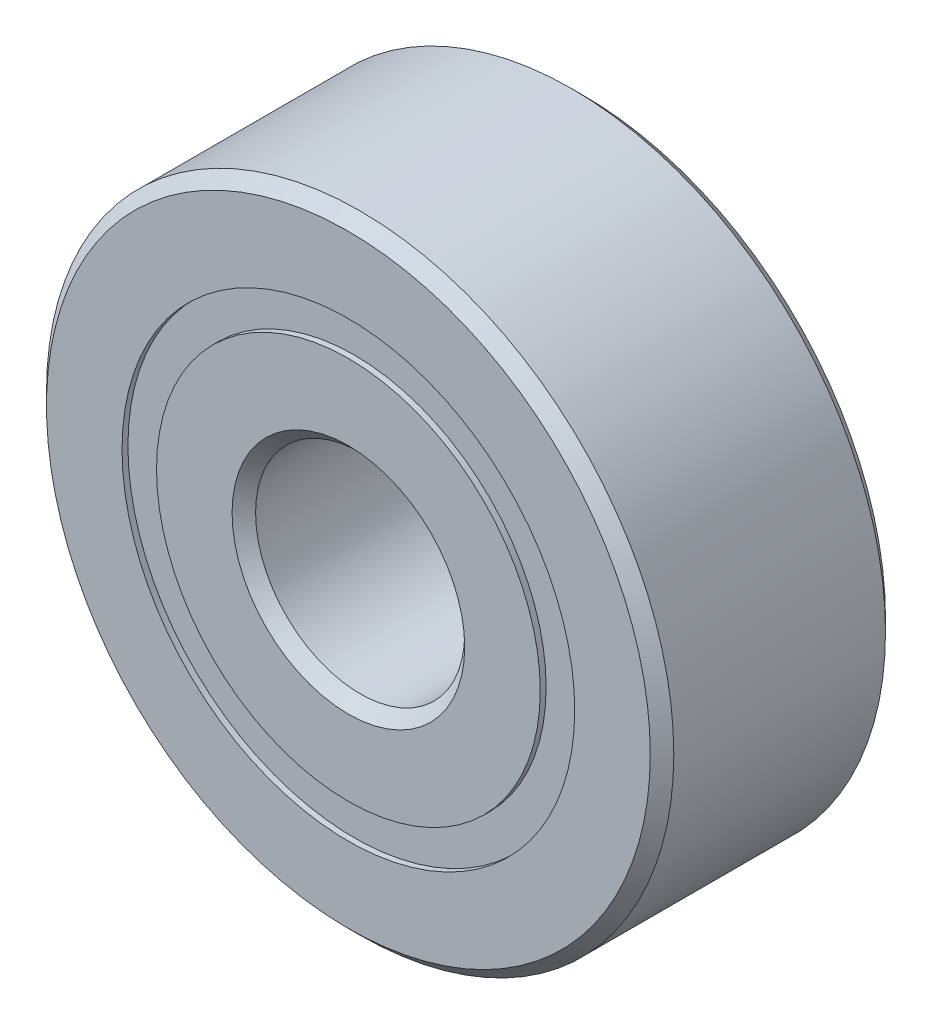
SolidWorks part; units mm, degrees
material "Cast Alloy Steel"
ref_plane "Front Plane" through (0, 0, 0) normal (0, 0, 1) x (1, 0, 0)
ref_plane "Top Plane" through (0, 0, 0) normal (0, 1, 0) x (1, 0, 0)
ref_plane "Right Plane" through (0, 0, 0) normal (1, 0, 0) x (0, 0, -1)
sketch "Sketch1" plane through (0, 0, 0) normal (1, 0, 0) x (0, 0, -1)
  line L0 (-3.5719, 0) -> (3.5719, 0) construction
  line L1 (0, 9.525) -> (0, -9.525) construction
  line L2 (3.2147, 9.525) -> (-3.2147, 9.525)
  line L3 (-3.2147, 9.525) -> (-3.5719, 9.1678)
  line L4 (-3.5719, 9.1678) -> (-3.5719, 6.8734)
  line L5 (-3.5719, 6.8734) -> (-1.5875, 6.8734)
  line L6 (3.5719, 6.8734) -> (1.5875, 6.8734)
  line L7 (3.5719, 9.1678) -> (3.5719, 6.8734)
  line L8 (3.2147, 9.525) -> (3.5719, 9.1678)
  line L9 (0, 9.525) -> (0, 6.35) construction
  line L10 (0, 6.35) -> (0, 3.175) construction
  arc A0 (-1.5875, 6.8734) -> (1.5875, 6.8734) centre (0, 6.35) cw
  point P14 (0, 3.175)
  dimension "Width" = 7.1437
  dimension "OD" = 19.05
  dimension "D1" = 45
  dimension "D2" = 0.3572
  dimension "Shaft Dia" = 6.35
  dimension "D3" = 3.175
  dimension "D4" = 0.5234
revolve "Revolve1" add sketch "Sketch1" angle 360 about L0
sketch "Sketch3" plane through (0, 0, 0) normal (1, 0, 0) x (0, 0, -1)
  line L0 (-3.5719, 5.8266) -> (-1.5875, 5.8266)
  line L1 (0, 9.525) -> (0, -9.525) construction
  line L2 (-3.5719, 9.1678) -> (-3.5719, 6.8734) construction
  line L3 (-3.5719, 5.8266) -> (-3.5719, 3.5322)
  line L4 (-3.2147, 9.525) -> (-3.5719, 9.1678) construction
  line L5 (-3.5719, 3.5322) -> (-3.2147, 3.175)
  line L6 (-3.2147, 3.175) -> (3.2147, 3.175)
  line L7 (3.2147, 9.525) -> (3.2147, -9.525) construction
  line L8 (3.2147, 3.175) -> (3.5719, 3.5322)
  line L9 (3.5719, -9.1678) -> (3.5719, 9.1678) construction
  line L10 (3.5719, 3.5322) -> (3.5719, 5.8266)
  line L11 (3.5719, 5.8266) -> (1.5875, 5.8266)
  line L13 (3.2147, 9.525) -> (3.5719, 9.1678) construction
  arc A0 (1.5875, 6.8734) -> (-1.5875, 6.8734) centre (0, 6.35) ccw construction
  arc A1 (1.5875, 5.8266) -> (-1.5875, 5.8266) centre (0, 6.35) cw
revolve "Revolve3" add sketch "Sketch3" angle 360 about L0
sketch "Sketch4" plane through (0, 0, 0) normal (1, 0, 0) x (0, 0, -1)
  line L0 (-1.6715, 6.35) -> (1.6715, 6.35)
  arc A2 (-1.6715, 6.35) -> (1.6715, 6.35) centre (0, 6.35) cw
  arc A3 (1.5875, 6.8734) -> (-1.5875, 6.8734) centre (0, 6.35) ccw construction
revolve "Revolve4" add sketch "Sketch4" angle 360 about L0
ref_axis "Axis1" through (0, 0, -3.5719) along (0, 0, 1)
pattern_circular "CirPattern1" count 8 every 45 about axis through (0, 0, -3.5719) along (0, 0, 1) of bodies 104
sketch "Sketch5" plane through (0, 0, 0) normal (1, 0, 0) x (0, 0, -1)
  line L0 (-3.5719, 6.8734) -> (-1.5875, 6.8734) construction
  line L1 (-3.3933, 6.8734) -> (-1.6715, 6.8734)
  line L2 (-3.3933, 6.8734) -> (-3.3933, 5.8266)
  line L3 (-3.3933, 5.8266) -> (-1.6715, 5.8266)
  line L4 (-1.6715, 6.8734) -> (-1.6715, 5.8266)
  line L5 (-3.5719, 5.8266) -> (-1.5875, 5.8266) construction
  line L6 (3.5719, 6.8734) -> (1.5875, 6.8734) construction
  line L7 (3.3933, 6.8734) -> (1.6715, 6.8734)
  line L8 (3.3933, 6.8734) -> (3.3933, 5.8266)
  line L9 (3.3933, 5.8266) -> (1.6715, 5.8266)
  line L10 (1.6715, 6.8734) -> (1.6715, 5.8266)
  line L11 (3.5719, 5.8266) -> (1.5875, 5.8266) construction
  line L12 (-3.2147, 9.525) -> (-3.5719, 9.1678) construction
  point P18 (-3.3933, 9.3464)
revolve "Revolve5" add sketch "Sketch5" angle 360 about L0
move or copy body "Body-Move/Copy1" [suppressed] bodies to move or copy 101 103 104 122 123 124 125 126 127 128 137 138
equation "\"D2@Sketch1\" = \"Width@Sketch1\"*.05"
equation "\"D3@Sketch1\" = \"Width@Sketch1\"/2.25"
equation "\"D4@Sketch1\" = (((\"OD@Sketch1\"-\"Width@Sketch1\")/2)/3.25)/3.5"
equation "\"D2@CirPattern1\" = 360/\"Balls@CirPattern1\""
